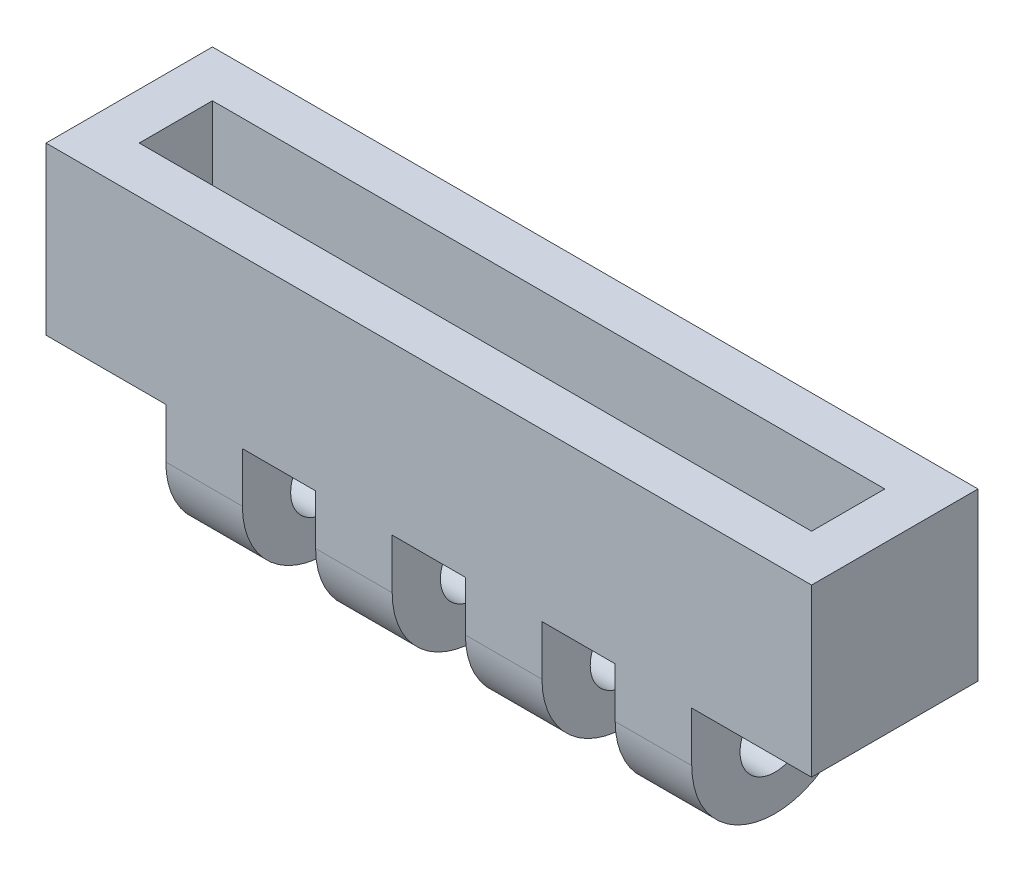
SolidWorks part; units mm, degrees
ref_plane "Front Plane" through (0, 0, 0) normal (0, 0, 1) x (1, 0, 0)
ref_plane "Top Plane" through (0, 0, 0) normal (0, 1, 0) x (1, 0, 0)
ref_plane "Right Plane" through (0, 0, 0) normal (1, 0, 0) x (0, 0, -1)
sketch "Sketch1" plane through (0, 0, 0) normal (0, 1, 0) x (1, 0, 0)
  line L1 (23, 5) -> (-23, 5)
  line L2 (23, 5) -> (23, -5)
  line L3 (23, -5) -> (-23, -5)
  line L4 (-23, 5) -> (-23, -5)
  line L5 (23, 5) -> (-23, -5) construction
  line L6 (23, -5) -> (-23, 5) construction
  point P0 (0, 0)
extrude "Boss-Extrude1" add sketch "Sketch1" along normal blind 10
shell "Shell1" thickness 2.8 removed face at (0, 10, 0)
sketch "Sketch2" plane through (0, 0, 0) normal (0, -1, 0) x (1, 0, 0)
  line L0 (23, -5) -> (-23, -5) construction
  line L1 (15.8, -5) -> (11.2, -5)
  line L2 (15.8, -5) -> (15.8, 5)
  line L3 (15.8, 5) -> (11.2, 5)
  line L4 (11.2, -5) -> (11.2, 5)
  line L5 (13.5, 5) -> (13.5, -5) construction
  line L6 (15.8, 0) -> (11.2, 0) construction
  line L7 (-23, 5) -> (23, 5) construction
  point P272 (13.5, 0)
  dimension "D2" = 4.6
extrude "Boss-Extrude2" add sketch "Sketch2" along normal blind 8
fillet "Fillet1" radius 5 2 edges at (13.5, -8, -5) (13.5, -8, 5)
pattern_linear "LPattern1" count 4 spacing 9 along (-1, 0, 0) of "Boss-Extrude2", "Fillet1"
sketch "Sketch4" plane through (15.8, 0, 0) normal (1, 0, 0) x (0, 0, -1)
  circle A0 centre (0, -3.74) radius 2.1
extrude "Cut-Extrude1" cut sketch "Sketch4" against normal through all
